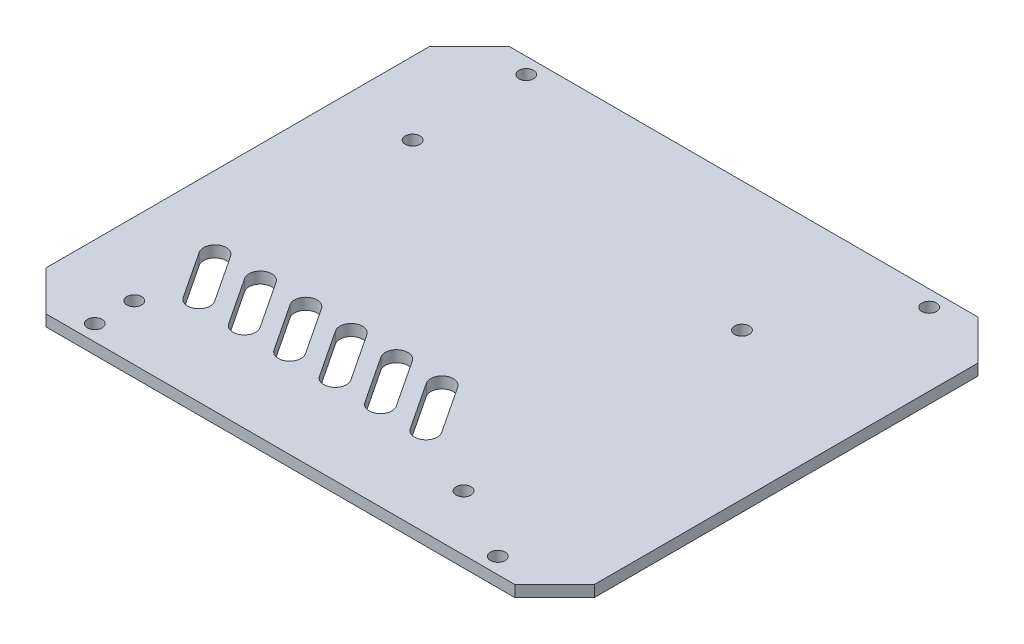
SolidWorks part; units mm, degrees
ref_plane "前视基准面" through (0, 0, 0) normal (0, 0, 1) x (1, 0, 0)
ref_plane "上视基准面" through (0, 0, 0) normal (0, 1, 0) x (1, 0, 0)
ref_plane "右视基准面" through (0, 0, 0) normal (1, 0, 0) x (0, 0, -1)
sketch "草图1" plane through (0, -19.39, 0) normal (0, -1, 0) x (1, 0, 0)
  line L16 (-51.8, -40.2958) -> (-44.7958, -47.3)
  line L17 (-44.7958, -47.3) -> (37.7958, -47.3)
  line L18 (37.7958, -47.3) -> (44.8, -40.2958)
  line L19 (44.8, -40.2958) -> (44.8, 27.2958)
  line L20 (44.8, 27.2958) -> (37.7958, 34.3)
  line L21 (-51.8, 27.2958) -> (-51.8, -40.2958)
  line L22 (37.7958, 34.3) -> (-44.7958, 34.3)
  line L23 (-44.7958, 34.3) -> (-51.8, 27.2958)
  line L24 (-51.8, -40.2958) -> (-44.7958, -47.3)
  line L25 (-44.7958, -47.3) -> (37.7958, -47.3)
  line L26 (37.7958, -47.3) -> (44.8, -40.2958)
  line L27 (44.8, -40.2958) -> (44.8, 27.2958)
  line L28 (44.8, 27.2958) -> (37.7958, 34.3)
  line L29 (-51.8, 27.2958) -> (-51.8, -40.2958)
  line L30 (37.7958, 34.3) -> (-44.7958, 34.3)
  line L31 (-44.7958, 34.3) -> (-51.8, 27.2958)
  dimension "D2" = 96.6
  dimension "D3" = 81.6
  dimension "D1" = 0.2
extrude "凸台-拉伸1" add sketch "草图1" along normal blind 2
sketch "草图2" plane through (0, -21.39, 0) normal (0, -1, 0) x (1, 0, 0)
  circle A0 centre (-39.0116, -24.5) radius 1.3
  circle A1 centre (19, -24.5) radius 1.3
  circle A2 centre (-39.0116, 24.5352) radius 1.3
  circle A3 centre (19, 24.5352) radius 1.3
  dimension "D1" = 2.6
extrude "切除-拉伸1" cut sketch "草图2" against normal up to next
sketch "草图3" plane through (0, -21.39, 0) normal (0, -1, 0) x (1, 0, 0)
  circle A0 centre (32, -44.5) radius 1.3 construction
  circle A1 centre (-39, -44.5) radius 1.3 construction
  circle A2 centre (32, 31.5) radius 1.3 construction
  circle A3 centre (-39, 31.5) radius 1.3 construction
  circle A4 centre (32, -44.5) radius 1.3
  circle A5 centre (-39, -44.5) radius 1.3
  circle A6 centre (32, 31.5) radius 1.3
  circle A7 centre (-39, 31.5) radius 1.3
extrude "切除-拉伸2" cut sketch "草图3" against normal up to next
sketch "草图4" plane through (0, -21.39, 0) normal (0, -1, 0) x (1, 0, 0)
  line L0 (-38.9928, 31.6194) -> (-39.0044, 24.6546) construction
  line L1 (-39.0282, 10.3) -> (-33.5143, 18.6425) construction
  line L2 (-40.6967, 11.4028) -> (-35.1828, 19.7453)
  line L3 (-37.3597, 9.1972) -> (-31.8458, 17.5397)
  line L5 (37.7958, 34.3) -> (-44.7958, 34.3) construction
  line L6 (-31.0282, 10.3) -> (-25.5143, 18.6425) construction
  line L9 (-32.6967, 11.4028) -> (-27.1828, 19.7453)
  line L12 (-29.3597, 9.1972) -> (-23.8458, 17.5397)
  line L15 (-23.0282, 10.3) -> (-17.5143, 18.6425) construction
  line L18 (-24.6967, 11.4028) -> (-19.1828, 19.7453)
  line L21 (-21.3597, 9.1972) -> (-15.8458, 17.5397)
  line L22 (-15.0282, 10.3) -> (-9.5143, 18.6425) construction
  line L23 (-16.6967, 11.4028) -> (-11.1828, 19.7453)
  line L24 (-13.3597, 9.1972) -> (-7.8458, 17.5397)
  line L25 (-7.0282, 10.3) -> (-1.5143, 18.6425) construction
  line L26 (-8.6967, 11.4028) -> (-3.1828, 19.7453)
  line L27 (-5.3597, 9.1972) -> (0.1542, 17.5397)
  line L28 (0.9718, 10.3) -> (6.4857, 18.6425) construction
  line L29 (-0.6967, 11.4028) -> (4.8172, 19.7453)
  line L30 (2.6403, 9.1972) -> (8.1542, 17.5397)
  arc A0 (-40.6967, 11.4028) -> (-37.3597, 9.1972) centre (-39.0282, 10.3) ccw
  arc A1 (-31.8458, 17.5397) -> (-35.1828, 19.7453) centre (-33.5143, 18.6425) ccw
  arc A12 (-32.6967, 11.4028) -> (-29.3597, 9.1972) centre (-31.0282, 10.3) ccw
  arc A13 (-23.8458, 17.5397) -> (-27.1828, 19.7453) centre (-25.5143, 18.6425) ccw
  arc A14 (-24.6967, 11.4028) -> (-21.3597, 9.1972) centre (-23.0282, 10.3) ccw
  arc A15 (-15.8458, 17.5397) -> (-19.1828, 19.7453) centre (-17.5143, 18.6425) ccw
  arc A16 (-16.6967, 11.4028) -> (-13.3597, 9.1972) centre (-15.0282, 10.3) ccw
  arc A17 (-7.8458, 17.5397) -> (-11.1828, 19.7453) centre (-9.5143, 18.6425) ccw
  arc A18 (-8.6967, 11.4028) -> (-5.3597, 9.1972) centre (-7.0282, 10.3) ccw
  arc A19 (0.1542, 17.5397) -> (-3.1828, 19.7453) centre (-1.5143, 18.6425) ccw
  arc A20 (-0.6967, 11.4028) -> (2.6403, 9.1972) centre (0.9718, 10.3) ccw
  arc A21 (8.1542, 17.5397) -> (4.8172, 19.7453) centre (6.4857, 18.6425) ccw
  point P6 (-36.2713, 14.4713)
  point P15 (-28.2713, 14.4713)
  point P22 (-20.2713, 14.4713)
  point P29 (-12.2713, 14.4713)
  point P36 (-4.2713, 14.4713)
  point P43 (3.7287, 14.4713)
  dimension "D1" = 2
  dimension "D2" = 10
  dimension "D3" = 5.5
  dimension "D4" = 12.8
  dimension "D5" = 24
  dimension "D6" = 6
extrude "切除-拉伸3" cut sketch "草图4" against normal up to next
sketch "草图5" plane through (0, -21.39, 0) normal (0, -1, 0) x (1, 0, 0)
sketch_block_instance "块1-1"
sketch_block "块1"
sketch "草图6" plane through (0, -19.39, 0) normal (0, 1, 0) x (1, 0, 0)
  line L0 (-39.0322, 2.6968) -> (-34.8198, 0.2624) construction
  line L1 (-34.177, 0.2624) -> (-29.9873, 2.7014) construction
  line L2 (-29.9828, 3.2622) -> (-34.0539, 5.6966) construction
  line L3 (-29.6682, 9.5398) -> (-30.5435, 10.0367) construction
  line L4 (-30.6757, 9.9592) -> (-30.6757, 7.9487) construction
  line L5 (-30.6301, 7.8712) -> (-29.7548, 7.3788) construction
  line L6 (-29.6226, 7.4564) -> (-29.6226, 9.4623) construction
  line L7 (-33.3108, 9.1249) -> (-33.3108, 8.049) construction
  line L8 (-33.2652, 7.9715) -> (-32.8731, 7.7527) construction
  line L9 (-32.8458, 9.0109) -> (-33.2652, 9.2207) construction
  line L10 (-33.2652, 9.2207) -> (-33.2652, 10.0868) construction
  line L11 (-32.791, 9.8224) -> (-33.2652, 10.0868) construction
  line L12 (-34.3274, 7.7345) -> (-32.823, 6.8819) construction
  line L13 (-34.373, 12.0335) -> (-34.373, 7.8119) construction
  line L14 (-33.3563, 11.6095) -> (-34.2408, 12.111) construction
  line L15 (-33.3108, 10.1644) -> (-33.3108, 11.532) construction
  line L16 (-33.3108, 9.1249) -> (-33.3108, 10.1644) construction
  line L17 (-17.9609, 5.9474) -> (-18.6265, 5.6829) construction
  line L18 (-17.7011, 5.0538) -> (-17.0627, 4.2514) construction
  line L19 (-19.6477, 6.6221) -> (-18.9684, 6.9093) construction
  line L20 (-20.2085, 7.429) -> (-20.9333, 8.3134) construction
  line L21 (-10.1469, 9.1523) -> (-9.7593, 9.1523) construction
  line L22 (-5.5196, 7.1144) -> (-5.5196, 7.7664) construction
  line L23 (-26.0439, 6.3576) -> (-26.0439, 4.2651) construction
  line L24 (-26.0439, 4.2651) -> (-25.2871, 4.2651) construction
  line L25 (-25.2597, 6.3576) -> (-26.0439, 6.3576) construction
  line L26 (-26.7095, 3.7272) -> (-26.7095, 8.979) construction
  line L27 (-26.7095, 8.979) -> (-26.0439, 8.979) construction
  line L28 (-26.0439, 8.979) -> (-26.0439, 6.8956) construction
  line L29 (-26.0439, 6.8956) -> (-25.1731, 6.8956) construction
  line L30 (-25.2096, 3.7272) -> (-26.7095, 3.7272) construction
  line L31 (-33.1558, -0.189) -> (-33.8122, -0.5719) construction
  line L32 (-35.189, -0.5719) -> (-35.8455, -0.189) construction
  line L33 (-35.8455, -0.189) -> (-39.2511, 1.7759) construction
  line L34 (-39.2511, 1.7759) -> (-39.9076, 2.1543) construction
  line L35 (-40.596, 3.3442) -> (-40.596, 8.7967) construction
  line L36 (-39.9076, 9.9866) -> (-39.2511, 10.365) construction
  line L37 (-39.2511, 10.365) -> (-35.8455, 12.3299) construction
  line L38 (-35.8455, 12.3299) -> (-35.189, 12.7128) construction
  line L39 (-33.8122, 12.7128) -> (-33.1558, 12.3299) construction
  line L40 (-33.1558, 12.3299) -> (-29.7503, 10.365) construction
  line L41 (-29.7503, 10.365) -> (-29.0938, 9.9866) construction
  line L42 (-28.4054, 8.7967) -> (-28.4054, 3.3442) construction
  line L43 (-29.0938, 2.1543) -> (-29.7503, 1.7759) construction
  line L44 (-29.7503, 1.7759) -> (-33.1558, -0.189) construction
  line L45 (-5.3737, 8.5687) -> (-5.2826, 8.979) construction
  line L46 (-5.2826, 8.979) -> (-4.2431, 8.979) construction
  line L47 (-4.2431, 8.979) -> (-4.2431, 6.6631) construction
  line L48 (-7.6486, 5.3365) -> (-7.2018, 6.1753) construction
  line L49 (-5.4056, 8.5687) -> (-5.3737, 8.5687) construction
  line L50 (-8.0133, 5.8243) -> (-8.0133, 4.9034) construction
  line L51 (-8.0133, 4.9034) -> (-9.5086, 4.9034) construction
  line L52 (-11.3094, 7.3378) -> (-11.3094, 7.3652) construction
  line L53 (-11.3869, 8.8286) -> (-11.3869, 8.8651) construction
  line L54 (-9.5178, 8.1767) -> (-10.1606, 8.1767) construction
  line L55 (-8.6424, 5.8243) -> (-8.0133, 5.8243) construction
  line L56 (-13.8761, 4.9034) -> (-13.8761, 7.5749) construction
  line L57 (-15.0295, 7.2649) -> (-15.0295, 4.9034) construction
  line L58 (-15.0295, 4.9034) -> (-16.3014, 4.9034) construction
  line L59 (-16.3014, 4.9034) -> (-16.3014, 7.4245) construction
  line L60 (-13.7575, 8.4183) -> (-13.7302, 8.4183) construction
  line L61 (-13.7302, 8.4183) -> (-13.639, 8.979) construction
  line L62 (-13.639, 8.979) -> (-12.5996, 8.979) construction
  line L63 (-12.5996, 8.979) -> (-12.5996, 4.9034) construction
  line L64 (-12.5996, 4.9034) -> (-13.8761, 4.9034) construction
  line L65 (-21.7265, 8.979) -> (-21.7265, 5.0857) construction
  line L66 (-22.3785, 8.979) -> (-21.7265, 8.979) construction
  line L67 (-22.3785, 5.0857) -> (-22.3785, 8.979) construction
  line L68 (-21.7265, 5.0857) -> (-22.3785, 5.0857) construction
  line L69 (-3.4042, 8.979) -> (-2.1368, 8.979) construction
  line L70 (-2.1368, 8.979) -> (-2.1368, 6.6494) construction
  line L71 (-0.8102, 5.9838) -> (-0.596, 4.8851) construction
  line L72 (-2.2508, 5.61) -> (-2.2782, 5.61) construction
  line L73 (-2.2782, 5.61) -> (-2.3648, 4.9034) construction
  line L74 (-2.3648, 4.9034) -> (-3.4042, 4.9034) construction
  line L75 (-3.4042, 4.9034) -> (-3.4042, 8.979) construction
  line L76 (-39.0322, 2.6968) -> (-34.8198, 0.2624)
  line L77 (-34.177, 0.2624) -> (-29.9873, 2.7014)
  line L78 (-29.9828, 3.2622) -> (-34.0539, 5.6966)
  line L79 (-29.6682, 9.5398) -> (-30.5435, 10.0367)
  line L80 (-30.6757, 9.9592) -> (-30.6757, 7.9487)
  line L81 (-30.6301, 7.8712) -> (-29.7548, 7.3788)
  line L82 (-29.6226, 7.4564) -> (-29.6226, 9.4623)
  line L83 (-33.3108, 9.1249) -> (-33.3108, 8.049)
  line L84 (-33.2652, 7.9715) -> (-32.8731, 7.7527)
  line L85 (-32.8458, 9.0109) -> (-33.2652, 9.2207)
  line L86 (-33.2652, 9.2207) -> (-33.2652, 10.0868)
  line L87 (-32.791, 9.8224) -> (-33.2652, 10.0868)
  line L88 (-34.3274, 7.7345) -> (-32.823, 6.8819)
  line L89 (-34.373, 12.0335) -> (-34.373, 7.8119)
  line L90 (-33.3563, 11.6095) -> (-34.2408, 12.111)
  line L91 (-33.3108, 10.1644) -> (-33.3108, 11.532)
  line L92 (-33.3108, 9.1249) -> (-33.3108, 10.1644)
  line L93 (-17.9609, 5.9474) -> (-18.6265, 5.6829)
  line L94 (-17.7011, 5.0538) -> (-17.0627, 4.2514)
  line L95 (-19.6477, 6.6221) -> (-18.9684, 6.9093)
  line L96 (-20.2085, 7.429) -> (-20.9333, 8.3134)
  line L97 (-10.1469, 9.1523) -> (-9.7593, 9.1523)
  line L98 (-5.5196, 7.1144) -> (-5.5196, 7.7664)
  line L99 (-26.0439, 6.3576) -> (-26.0439, 4.2651)
  line L100 (-26.0439, 4.2651) -> (-25.2871, 4.2651)
  line L101 (-25.2597, 6.3576) -> (-26.0439, 6.3576)
  line L102 (-26.7095, 3.7272) -> (-26.7095, 8.979)
  line L103 (-26.7095, 8.979) -> (-26.0439, 8.979)
  line L104 (-26.0439, 8.979) -> (-26.0439, 6.8956)
  line L105 (-26.0439, 6.8956) -> (-25.1731, 6.8956)
  line L106 (-25.2096, 3.7272) -> (-26.7095, 3.7272)
  line L107 (-33.1558, -0.189) -> (-33.8122, -0.5719)
  line L108 (-35.189, -0.5719) -> (-35.8455, -0.189)
  line L109 (-35.8455, -0.189) -> (-39.2511, 1.7759)
  line L110 (-39.2511, 1.7759) -> (-39.9076, 2.1543)
  line L111 (-40.596, 3.3442) -> (-40.596, 8.7967)
  line L112 (-39.9076, 9.9866) -> (-39.2511, 10.365)
  line L113 (-39.2511, 10.365) -> (-35.8455, 12.3299)
  line L114 (-35.8455, 12.3299) -> (-35.189, 12.7128)
  line L115 (-33.8122, 12.7128) -> (-33.1558, 12.3299)
  line L116 (-33.1558, 12.3299) -> (-29.7503, 10.365)
  line L117 (-29.7503, 10.365) -> (-29.0938, 9.9866)
  line L118 (-28.4054, 8.7967) -> (-28.4054, 3.3442)
  line L119 (-29.0938, 2.1543) -> (-29.7503, 1.7759)
  line L120 (-29.7503, 1.7759) -> (-33.1558, -0.189)
  line L121 (-5.3737, 8.5687) -> (-5.2826, 8.979)
  line L122 (-5.2826, 8.979) -> (-4.2431, 8.979)
  line L123 (-4.2431, 8.979) -> (-4.2431, 6.6631)
  line L124 (-7.6486, 5.3365) -> (-7.2018, 6.1753)
  line L125 (-5.4056, 8.5687) -> (-5.3737, 8.5687)
  line L126 (-8.0133, 5.8243) -> (-8.0133, 4.9034)
  line L127 (-8.0133, 4.9034) -> (-9.5086, 4.9034)
  line L128 (-11.3094, 7.3378) -> (-11.3094, 7.3652)
  line L129 (-11.3869, 8.8286) -> (-11.3869, 8.8651)
  line L130 (-9.5178, 8.1767) -> (-10.1606, 8.1767)
  line L131 (-8.6424, 5.8243) -> (-8.0133, 5.8243)
  line L132 (-13.8761, 4.9034) -> (-13.8761, 7.5749)
  line L133 (-15.0295, 7.2649) -> (-15.0295, 4.9034)
  line L134 (-15.0295, 4.9034) -> (-16.3014, 4.9034)
  line L135 (-16.3014, 4.9034) -> (-16.3014, 7.4245)
  line L136 (-13.7575, 8.4183) -> (-13.7302, 8.4183)
  line L137 (-13.7302, 8.4183) -> (-13.639, 8.979)
  line L138 (-13.639, 8.979) -> (-12.5996, 8.979)
  line L139 (-12.5996, 8.979) -> (-12.5996, 4.9034)
  line L140 (-12.5996, 4.9034) -> (-13.8761, 4.9034)
  line L141 (-21.7265, 8.979) -> (-21.7265, 5.0857)
  line L142 (-22.3785, 8.979) -> (-21.7265, 8.979)
  line L143 (-22.3785, 5.0857) -> (-22.3785, 8.979)
  line L144 (-21.7265, 5.0857) -> (-22.3785, 5.0857)
  line L145 (-3.4042, 8.979) -> (-2.1368, 8.979)
  line L146 (-2.1368, 8.979) -> (-2.1368, 6.6494)
  line L147 (-0.8102, 5.9838) -> (-0.596, 4.8851)
  line L148 (-2.2508, 5.61) -> (-2.2782, 5.61)
  line L149 (-2.2782, 5.61) -> (-2.3648, 4.9034)
  line L150 (-2.3648, 4.9034) -> (-3.4042, 4.9034)
  line L151 (-3.4042, 4.9034) -> (-3.4042, 8.979)
  spline S0 degree 3 poles (1947.2043, 259.0221) (-2040.5975, -86.3945) (1971.5647, -86.1046) (-2015.9835, 259.8919) knots -24.014283 -24.014283 -24.014283 -24.014283 31.060476 31.060476 31.060476 31.060476 only from (-34.8198, 0.2624) to (-34.177, 0.2624) construction
  spline S1 degree 3 poles (-178.8618, 1996.4067) (-13.3017, -2002.4803) (85.7628, 2005.1657) (-277.1173, -1980.6649) knots -12.069605 -12.069605 -12.069605 -12.069605 23.053377 23.053377 23.053377 23.053377 only from (-29.9873, 2.7014) to (-29.9828, 3.2622) construction
  spline S2 degree 3 poles (-2011.9647, -280.5218) (1973.0796, 101.2598) (-2042.0834, 101.2623) (1942.99, -280.5143) knots -16.956312 -16.956312 -16.956312 -16.956312 31.955994 31.955994 31.955994 31.955994 only from (-34.0539, 5.6966) to (-34.9429, 5.6966) construction
  spline S3 degree 2 poles (1696.8938, 1005.9909) (-1772.9636, -998.1959) (1692.7429, 1003.6514) knots -19.544322 -19.544322 -19.544322 21.524182 21.524182 21.524182 only from (-34.9429, 5.6966) to (-39.0732, 3.3123) construction
  spline S4 degree 3 poles (312.9236, -1964.6822) (-255.5836, 1997.2947) (39.8207, -2001.4292) (20.6091, 2000.9771) knots -16.033039 -16.033039 -16.033039 -16.033039 19.060221 19.060221 19.060221 19.060221 only from (-39.0732, 3.3123) to (-39.0322, 2.6968) construction
  spline S5 degree 3 poles (1612.1466, 1139.1382) (-173.749, 124.6775) (-29.5451, -1.4055) (-29.5451, 6.2482) (-29.5451, 12.5795) (-131.1047, 41.0713) (891.7703, -1766.7786) knots -20.983072 -20.983072 -20.983072 -20.983072 3 3 3 23.1269 23.1269 23.1269 23.1269 only from (-30.1469, 6.0431) to (-30.1469, 7.1281) construction
  spline S6 degree 3 poles (-1593.6748, -1232.4433) (112.4759, -108.2288) (-30.7532, 14.45) (-30.7532, 6.9321) (-30.7532, 0.2328) (76.6581, -24.0346) (-1002.5668, 1752.6044) knots -22.899222 -22.899222 -22.899222 -22.899222 1 1 1 21.696321 21.696321 21.696321 21.696321 only from (-30.1469, 7.1281) to (-30.1469, 6.0431) construction
  spline S7 degree 3 poles (-1735.267, -1035.1971) (1720.3132, 981.2712) (-1822.079, -884.2768) (1795.5461, 824.5182) knots -24.864003 -24.864003 -24.864003 -24.864003 29.805716 29.805716 29.805716 29.805716 only from (-30.5435, 10.0367) to (-30.6757, 9.9592) construction
  spline S8 degree 3 poles (1803.8452, -787.8206) (-1835.1338, 879.7734) (1736.3613, -937.8925) (-1752.2845, 1025.0132) knots -52.644856 -52.644856 -52.644856 -52.644856 63.422153 63.422153 63.422153 63.422153 only from (-30.6757, 7.9487) to (-30.6301, 7.8712) construction
  spline S9 degree 3 poles (1675.9971, 1050.9308) (-1781.5786, -962.103) (1762.6814, 899.8753) (-1856.6746, -805.2277) knots -20.869425 -20.869425 -20.869425 -20.869425 33.809897 33.809897 33.809897 33.809897 only from (-29.7548, 7.3788) to (-29.6226, 7.4564) construction
  spline S10 degree 3 poles (-1017.153, 1748.416) (898.1967, -1765.8691) (-895.3334, 1815.971) (771.5167, -1822.726) knots -45.73326 -45.73326 -45.73326 -45.73326 46.535072 46.535072 46.535072 46.535072 only from (-29.6226, 9.4623) to (-29.6682, 9.5398) construction
  spline S11 degree 3 poles (1241.4728, -1544.2848) (-126.4363, -19.7603) (-21.5989, 9.5171) (-21.5989, 3.8639) (-21.5989, -3.1211) (-150.7291, 66.7677) (1747.5616, 931.244) knots -20.398043 -20.398043 -20.398043 -20.398043 3 3 3 28.967808 28.967808 28.967808 28.967808 only from (-22.0502, 4.2833) to (-22.0502, 3.44) construction
  spline S12 degree 3 poles (-1791.638, 931.233) (106.6275, 66.7672) (-22.5016, -3.1211) (-22.5016, 3.8639) (-22.5016, 9.5171) (82.3355, -19.7602) (-1285.567, -1544.2778) knots -24.967698 -24.967698 -24.967698 -24.967698 1 1 1 24.398007 24.398007 24.398007 24.398007 only from (-22.0502, 3.44) to (-22.0502, 4.2833) construction
  spline S13 degree 3 poles (953.112, -1731.5311) (-960.0271, 1783.9495) (831.3079, -1798.9714) (-833.3757, 1840.6921) knots -41.715469 -41.715469 -41.715469 -41.715469 50.515238 50.515238 50.515238 50.515238 only from (-33.3108, 8.049) to (-33.2652, 7.9715) construction
  spline S14 degree 3 poles (345.3515, -1953.7628) (-656.074, 2008.4671) (704.4049, -1945.0024) (-795.7723, 1856.1671) knots -18.836401 -18.836401 -18.836401 -18.836401 26.867419 26.867419 26.867419 26.867419 only from (-32.8731, 7.7527) to (-32.0799, 7.9031) construction
  spline S15 degree 3 poles (393.8329, 1947.428) (-1017.3565, -1766.8215) (1294.138, 1559.3727) (-1541.9229, -1298.5467) knots -37.738435 -37.738435 -37.738435 -37.738435 30.849118 30.849118 30.849118 30.849118 only from (-32.0799, 7.9031) to (-32.8458, 9.0109) construction
  spline S16 degree 3 poles (-1970.6267, 490.4514) (1900.3877, -652.3893) (-1909.3139, 822.203) (1735.9268, -921.8099) knots -2.984455 -2.984455 -2.984455 -2.984455 24.908291 24.908291 24.908291 24.908291 only from (-31.0405, 7.315) to (-32.791, 9.8224) construction
  spline S17 degree 3 poles (1301.0551, -1483.1694) (-1380.7778, 1570.3517) (1272.9624, -1585.6466) (-1251.2088, 1591.7607) knots -4.177868 -4.177868 -4.177868 -4.177868 21.267464 21.267464 21.267464 21.267464 only from (-32.823, 6.8819) to (-31.0405, 7.315) construction
  spline S18 degree 3 poles (-426.7908, -1953.0944) (416.9018, 1960.3516) (-543.6183, -1930.3492) (531.9657, 1925.7159) knots -40.574336 -40.574336 -40.574336 -40.574336 54.224541 54.224541 54.224541 54.224541 only from (-34.373, 7.8119) to (-34.3274, 7.7345) construction
  spline S19 degree 3 poles (-1739.7201, -1031.8845) (1717.3311, 982.0362) (-1826.4475, -880.8273) (1792.473, 825.1567) knots -21.867988 -21.867988 -21.867988 -21.867988 32.80886 32.80886 32.80886 32.80886 only from (-34.2408, 12.111) to (-34.373, 12.0335) construction
  spline S20 degree 3 poles (1326.5597, 1477.8337) (-1443.7748, -1422.5109) (1417.5131, 1403.8248) (-1515.2659, -1331.1895) knots -66.611259 -66.611259 -66.611259 -66.611259 68.63044 68.63044 68.63044 68.63044 only from (-33.3108, 11.532) to (-33.3563, 11.6095) construction
  spline S21 degree 3 poles (-1127.9465, 1668.9065) (1205.0665, -1581.8003) (-1320.6139, 1532.1331) (1326.4072, -1474.1074) knots -17.356672 -17.356672 -17.356672 -17.356672 19.212167 19.212167 19.212167 19.212167 only from (-18.6265, 5.6829) to (-19.4334, 5.0857) construction
  spline S22 degree 3 poles (1945.6237, -352.8331) (-1917.2958, 619.5498) (1753.4488, -897.6325) (-1594.6226, 1226.9154) knots -23.773694 -23.773694 -23.773694 -23.773694 31.399142 31.399142 31.399142 31.399142 only from (-19.4334, 5.0857) to (-18.7952, 4.6435) construction
  spline S23 degree 3 poles (-1957.8604, 491.3787) (1905.2875, -332.0334) (-1960.1859, 166.6666) (1980.2936, 44.6676) knots -22.175827 -22.175827 -22.175827 -22.175827 30.019969 30.019969 30.019969 30.019969 only from (-18.7952, 4.6435) to (-17.7011, 5.0538) construction
  spline S24 degree 3 poles (-1996.9289, 274.3391) (2008.3741, -55.5657) (-2041.9478, -141.8187) (1949.9756, 346.3582) knots -14.985955 -14.985955 -14.985955 -14.985955 26.624596 26.624596 26.624596 26.624596 only from (-17.0627, 4.2514) to (-18.7952, 3.5448) construction
  spline S25 degree 3 poles (-959.5674, 1764.5293) (1176.2874, -1603.5878) (-1432.6495, 1427.6748) (1567.7803, -1205.173) knots -7.558703 -7.558703 -7.558703 -7.558703 20.482777 20.482777 20.482777 20.482777 only from (-18.7952, 3.5448) to (-20.7327, 5.1587) construction
  spline S26 degree 3 poles (1924.0493, -458.54) (-2016.5165, 343.495) (1995.4741, -211.501) (-2016.1303, 116.1959) knots -7.852621 -7.852621 -7.852621 -7.852621 24.144848 24.144848 24.144848 24.144848 only from (-20.7327, 5.1587) to (-19.6477, 6.6221) construction
  spline S27 degree 3 poles (615.0637, -1888.8545) (-795.6899, 1841.0297) (868.9978, -1778.6578) (-986.0957, 1757.28) knots -9.138526 -9.138526 -9.138526 -9.138526 27.25787 27.25787 27.25787 27.25787 only from (-18.9684, 6.9093) to (-18.2162, 7.5111) construction
  spline S28 degree 3 poles (215.7009, 1986.9997) (-654.6592, -1923.8751) (894.6606, 1828.6602) (-1110.216, -1665.8008) knots -22.542702 -22.542702 -22.542702 -22.542702 37.658646 37.658646 37.658646 37.658646 only from (-18.2162, 7.5111) to (-18.9137, 7.9761) construction
  spline S29 degree 3 poles (-1605.429, -1208.7716) (1666.7814, 1140.7416) (-1773.5402, -1019.3674) (1765.9801, 905.5471) knots -8.791084 -8.791084 -8.791084 -8.791084 32.386114 32.386114 32.386114 32.386114 only from (-18.9137, 7.9761) to (-20.2085, 7.429) construction
  spline S30 degree 3 poles (1966.5787, -197.5818) (-2051.7497, -0.967) (2002.48, 224.4874) (-1974.8286, -400.794) knots -6.294928 -6.294928 -6.294928 -6.294928 33.756853 33.756853 33.756853 33.756853 only from (-20.9333, 8.3134) to (-18.9411, 9.0793) construction
  spline S31 degree 3 poles (124.1341, -1982.3989) (-457.1442, 1958.1164) (708.8959, -1855.2284) (-1015.0804, 1736.3895) knots 0.697384 0.697384 0.697384 0.697384 28.978211 28.978211 28.978211 28.978211 only from (-18.9411, 9.0793) to (-16.9033, 7.4108) construction
  spline S32 degree 3 poles (-1495.2544, 1354.2838) (1523.5493, -1377.9736) (-1538.1686, 1424.3054) (1353.4505, -1448.6746) knots -4.734801 -4.734801 -4.734801 -4.734801 40.265101 40.265101 40.265101 40.265101 only from (-16.9033, 7.4108) to (-17.9609, 5.9474) construction
  spline S33 degree 3 poles (-1961.8056, -418.0731) (126.6492, -101.6131) (-10.6711, 16.7967) (-10.6711, 6.2847) (-10.6711, -3.9538) (125.3735, 107.9903) (-1932.7785, 547.0377) knots -21.79377 -21.79377 -21.79377 -21.79377 3 3 3 27.67833 27.67833 27.67833 27.67833 only from (-10.156, 6.923) to (-10.156, 5.6556) construction
  spline S34 degree 3 poles (1882.1607, 641.7029) (-158.572, 123.862) (-9.6409, -4.6535) (-9.6409, 6.2847) (-9.6409, 17.5385) (-160.5965, -118.9677) (1923.9331, -488.0552) knots -25.364902 -25.364902 -25.364902 -25.364902 1 1 1 27.543492 27.543492 27.543492 27.543492 only from (-10.156, 5.6556) to (-10.156, 6.923) construction
  spline S35 degree 3 poles (398.3769, -1946.8651) (-621.0655, 1916.7975) (746.5301, -1849.6014) (-860.4662, 1818.6943) knots -20.367991 -20.367991 -20.367991 -20.367991 27.043685 27.043685 27.043685 27.043685 only from (-9.7593, 9.1523) to (-9.1667, 9.4441) construction
  spline S36 degree 3 poles (-1851.6901, 784.2948) (1770.8918, -932.7585) (-1685.1957, 1125.6418) (1512.1872, -1283.8884) knots -14.155704 -14.155704 -14.155704 -14.155704 26.455766 26.455766 26.455766 26.455766 only from (-9.1667, 9.4441) to (-10.0557, 9.8954) construction
  spline S37 degree 3 poles (-1999.7746, -177.9397) (2048.5506, 17.7992) (-2059.7856, 149.4036) (1971.6374, -249.0633) knots -24.53604 -24.53604 -24.53604 -24.53604 22.203045 22.203045 22.203045 22.203045 only from (-10.0557, 9.8954) to (-10.9219, 9.4668) construction
  spline S38 degree 3 poles (335.4233, 1977.3974) (-130.5762, -1935.4278) (-138.8194, 1950.0115) (386.7962, -1948.2187) knots -42.090152 -42.090152 -42.090152 -42.090152 46.007634 46.007634 46.007634 46.007634 only from (-10.9219, 9.4668) to (-10.7304, 9.1021) construction
  spline S39 degree 3 poles (-2000.164, -195.6542) (1968.231, 177.2652) (-1992.5781, -127.132) (1986.8184, 117.9013) knots -23.761314 -23.761314 -23.761314 -23.761314 27.411452 27.411452 27.411452 27.411452 only from (-10.7304, 9.1021) to (-10.1469, 9.1523) construction
  spline S40 degree 3 poles (1900.4815, 611.268) (-1853.5024, -713.4995) (1804.2956, 824.4669) (-1796.5625, -882.5407) knots -25.691977 -25.691977 -25.691977 -25.691977 25.491412 25.491412 25.491412 25.491412 only from (-5.5196, 7.7664) to (-6.135, 8.09) construction
  spline S41 degree 3 poles (-2003.4629, -52.8338) (2017.9029, -136.2777) (-2009.5197, 324.3726) (1939.2706, -450.8338) knots -29.27083 -29.27083 -29.27083 -29.27083 28.779665 28.779665 28.779665 28.779665 only from (-6.135, 8.09) to (-6.5727, 7.739) construction
  spline S42 degree 3 poles (-1965.4656, -395.4958) (1971.7383, 441.6954) (-1983.3474, -426.4496) (1951.4791, 419.1184) knots -18.272249 -18.272249 -18.272249 -18.272249 20.366917 20.366917 20.366917 20.366917 only from (-6.5727, 7.739) to (-5.5196, 7.1144) construction
  spline S43 degree 3 poles (-552.3477, -1916.0072) (39.6444, 1949.1893) (231.1798, -1947.9287) (-488.2476, 1949.0672) knots -16.951569 -16.951569 -16.951569 -16.951569 21.292276 21.292276 21.292276 21.292276 only from (-25.2871, 4.2651) to (-23.9011, 5.2681) construction
  spline S44 degree 3 poles (74.9674, -1978.7796) (-669.1868, 1491.4113) (1220.9961, -1007.5518) (-1925.4997, 576.7533) knots -20.703775 -20.703775 -20.703775 -20.703775 29.911591 29.911591 29.911591 29.911591 only from (-23.9011, 5.2681) to (-25.2597, 6.3576) construction
  spline S45 degree 3 poles (1967.7044, -102.3152) (-2083.6001, -202.2982) (1987.7708, 465.393) (-1913.3422, -643.1952) knots -12.662635 -12.662635 -12.662635 -12.662635 20.708978 20.708978 20.708978 20.708978 only from (-25.1731, 6.8956) to (-23.2401, 5.2681) construction
  spline S46 degree 3 poles (-1462.7137, 1393.5071) (1511.2501, -1404.3078) (-1580.4996, 1407.0991) (1432.7296, -1365.1759) knots -7.615095 -7.615095 -7.615095 -7.615095 23.693651 23.693651 23.693651 23.693651 only from (-23.2401, 5.2681) to (-25.2096, 3.7272) construction
  spline S47 degree 3 poles (-1986.2159, -424.6605) (1872.5149, 650.7296) (-1856.7008, -859.0204) (1668.1443, 1044.8861) knots -40.403395 -40.403395 -40.403395 -40.403395 46.454358 46.454358 46.454358 46.454358 only from (-33.8122, -0.5719) to (-34.5006, -0.7543) construction
  spline S48 degree 3 poles (-1740.3489, 1039.5921) (1790.0962, -854.0172) (-1943.0897, 646.2372) (1918.0006, -420.927) knots -38.373718 -38.373718 -38.373718 -38.373718 48.302597 48.302597 48.302597 48.302597 only from (-34.5006, -0.7543) to (-35.189, -0.5719) construction
  spline S49 degree 3 poles (-754.8971, 1867.8409) (885.9932, -1784.6) (-1157.7277, 1677.1962) (1246.9181, -1524.5355) knots -12.834285 -12.834285 -12.834285 -12.834285 29.798641 29.798641 29.798641 29.798641 only from (-39.9076, 2.1543) to (-40.596, 3.3442) construction
  spline S50 degree 3 poles (1310.7611, 1480.2732) (-1219.4015, -1620.1293) (943.9093, 1763.7167) (-807.2491, -1834.6442) knots -11.169927 -11.169927 -11.169927 -11.169927 32.277267 32.277267 32.277267 32.277267 only from (-40.596, 8.7967) to (-39.9076, 9.9866) construction
  spline S51 degree 3 poles (1829.5545, -704.5958) (-1983.3127, 518.655) (1959.6502, -271.0062) (-2031.7382, 64.4568) knots -28.630568 -28.630568 -28.630568 -28.630568 59.634843 59.634843 59.634843 59.634843 only from (-35.189, 12.7128) to (-34.5006, 12.8952) construction
  spline S52 degree 3 poles (1962.7022, 65.7414) (-2028.2181, -273.3756) (1913.3784, 521.8911) (-1897.0742, -708.4939) knots -29.74703 -29.74703 -29.74703 -29.74703 58.724161 58.724161 58.724161 58.724161 only from (-34.5006, 12.8952) to (-33.8122, 12.7128) construction
  spline S53 degree 3 poles (611.3262, -1882.3455) (-897.4898, 1821.8566) (1049.2417, -1687.0258) (-1295.1838, 1553.5314) knots -2.467628 -2.467628 -2.467628 -2.467628 41.506639 41.506639 41.506639 41.506639 only from (-29.0938, 9.9866) to (-28.4054, 8.7967) construction
  spline S54 degree 3 poles (-1230.5684, -1592.4268) (988.9215, 1738.3623) (-842.904, -1836.9675) (564.0724, 1910.0048) knots -0.095652 -0.095652 -0.095652 -0.095652 42.997123 42.997123 42.997123 42.997123 only from (-28.4054, 3.3442) to (-29.0938, 2.1543) construction
  spline S55 degree 3 poles (-1430.5573, 1407.5659) (1723.1127, -1481.9909) (-1919.6145, 1389.7982) (1763.4855, -917.7581) knots -7.107453 -7.107453 -7.107453 -7.107453 39.300169 39.300169 39.300169 39.300169 only from (-4.2431, 6.6631) to (-5.8934, 4.8031) construction
  spline S56 degree 3 poles (200.3126, 1993.6618) (-113.4143, -2029.6162) (37.9701, 2047.0917) (-46.8978, -1994.2146) knots -24.475698 -24.475698 -24.475698 -24.475698 28.452112 28.452112 28.452112 28.452112 only from (-5.8934, 4.8031) to (-7.6486, 5.3365) construction
  spline S57 degree 3 poles (-1933.6669, -520.0604) (1769.2026, 770.3694) (-1678.914, -975.8177) (1607.9896, 1184.3814) knots -29.345565 -29.345565 -29.345565 -29.345565 33.949512 33.949512 33.949512 33.949512 only from (-7.2018, 6.1753) to (-6.135, 5.8197) construction
  spline S58 degree 3 poles (-1709.7987, 1053.3931) (1749.403, -1046.8479) (-1793.7464, 1008.7473) (1793.1121, -866.6254) knots -20.675466 -20.675466 -20.675466 -20.675466 32.208493 32.208493 32.208493 32.208493 only from (-6.135, 5.8197) to (-5.5196, 6.3394) construction
  spline S59 degree 3 poles (1975.7527, -248.8039) (-1868.9813, 512.6632) (1631.6647, -894.331) (-1295.7423, 1512.4535) knots -12.733532 -12.733532 -12.733532 -12.733532 25.757539 25.757539 25.757539 25.757539 only from (-5.5196, 6.3394) to (-7.7854, 7.8393) construction
  spline S60 degree 3 poles (1042.4421, 1706.8309) (-834.6219, -1820.7719) (589.0356, 1925.2458) (-367.8223, -1955.7065) knots -11.03402 -11.03402 -11.03402 -11.03402 21.264003 21.264003 21.264003 21.264003 only from (-7.7854, 7.8393) to (-6.5727, 9.0793) construction
  spline S61 degree 3 poles (-582.1125, -1906.1013) (523.4678, 1965.3983) (-513.1262, -1956.0805) (513.8823, 1939.9285) knots -17.627726 -17.627726 -17.627726 -17.627726 33.245267 33.245267 33.245267 33.245267 only from (-6.5727, 9.0793) to (-5.4056, 8.5687) construction
  spline S62 degree 3 poles (-1930.5691, 559.3395) (1974.8488, -448.3348) (-2018.9786, 347.7304) (1976.7281, -218.5664) knots -33.500705 -33.500705 -33.500705 -33.500705 55.20773 55.20773 55.20773 55.20773 only from (-9.5086, 4.9034) to (-10.156, 4.8031) construction
  spline S63 degree 3 poles (-1999.2913, 198.6019) (2020.2524, -1.5641) (-2032.1384, -171.0059) (1955.7763, 357.6437) knots -3.872904 -3.872904 -3.872904 -3.872904 23.676976 23.676976 23.676976 23.676976 only from (-10.156, 4.8031) to (-11.8611, 6.2847) construction
  spline S64 degree 3 poles (1939.5115, 440.407) (-1940.4923, -577.4399) (1873.7743, 723.7895) (-1830.7521, -821.4821) knots -8.023341 -8.023341 -8.023341 -8.023341 31.752387 31.752387 31.752387 31.752387 only from (-11.8611, 6.2847) to (-11.3094, 7.3378) construction
  spline S65 degree 3 poles (-1329.9726, 1509.8665) (1428.2205, -1408.3534) (-1547.8279, 1317.3332) (1597.8765, -1177.5524) knots -10.762319 -10.762319 -10.762319 -10.762319 36.904963 36.904963 36.904963 36.904963 only from (-11.3094, 7.3652) to (-11.7608, 8.1265) construction
  spline S66 degree 3 poles (1690.5146, -1041.4074) (-1758.3489, 1014.3497) (1757.9984, -959.3158) (-1776.7351, 948.7003) knots -9.879735 -9.879735 -9.879735 -9.879735 41.23424 41.23424 41.23424 41.23424 only from (-11.7608, 8.1265) to (-11.3869, 8.8286) construction
  spline S67 degree 3 poles (-752.9374, 1842.3255) (1308.8718, -1353.5914) (-1702.759, 958.5145) (1892.0914, -582.47) knots -26.637538 -26.637538 -26.637538 -26.637538 53.487657 53.487657 53.487657 53.487657 only from (-11.3869, 8.8651) to (-11.9659, 9.6674) construction
  spline S68 degree 3 poles (1894.089, -594.3405) (-1996.6922, 519.1508) (2004.2706, -389.5025) (-1990.0486, 289.9866) knots 3.488718 3.488718 3.488718 3.488718 33.266204 33.266204 33.266204 33.266204 only from (-11.9659, 9.6674) to (-10.2563, 10.6932) construction
  spline S69 degree 3 poles (883.5316, -1769.7092) (-1265.933, 1528.3806) (1531.048, -1233.7757) (-1756.2499, 971.1381) knots 2.502912 2.502912 2.502912 2.502912 33.788332 33.788332 33.788332 33.788332 only from (-10.2563, 10.6932) to (-7.9495, 9.2207) construction
  spline S70 degree 3 poles (-1471.0119, 1372.7307) (1578.4938, -1482.6464) (-1566.0618, 1580.68) (1222.054, -1564.0225) knots 0.121158 0.121158 0.121158 0.121158 45.755216 45.755216 45.755216 45.755216 only from (-7.9495, 9.2207) to (-9.5178, 8.1767) construction
  spline S71 degree 3 poles (1988.9699, 46.517) (-2010.5704, -146.5098) (1966.0388, 323.2501) (-1936.5111, -524.1006) knots -22.92357 -22.92357 -22.92357 -22.92357 29.602258 29.602258 29.602258 29.602258 only from (-10.1606, 8.1767) to (-10.7623, 7.9031) construction
  spline S72 degree 3 poles (-533.5031, 1938.1422) (580.6394, -1888.8677) (-675.8787, 1879.566) (733.4353, -1848.486) knots -24.426858 -24.426858 -24.426858 -24.426858 29.596464 29.596464 29.596464 29.596464 only from (-10.7623, 7.9031) to (-10.6347, 7.6159) construction
  spline S73 degree 3 poles (1783.3603, -873.0273) (-1897.0996, 718.9291) (1929.1738, -548.4058) (-1965.9262, 421.9789) knots -49.380783 -49.380783 -49.380783 -49.380783 54.799618 54.799618 54.799618 54.799618 only from (-10.6347, 7.6159) to (-10.156, 7.6889) construction
  spline S74 degree 3 poles (1980.7033, 183.4675) (-2023.5442, -359.0617) (1962.1661, 541.9093) (-1888.572, -672.6294) knots -11.821996 -11.821996 -11.821996 -11.821996 18.874537 18.874537 18.874537 18.874537 only from (-10.156, 7.6889) to (-8.5285, 6.3212) construction
  spline S75 degree 3 poles (-1121.2007, -1655.0713) (1031.1489, 1733.8331) (-972.6532, -1765.1618) (877.4238, 1798.5447) knots -24.892551 -24.892551 -24.892551 -24.892551 35.36044 35.36044 35.36044 35.36044 only from (-8.5285, 6.3212) to (-8.6424, 5.8243) construction
  spline S76 degree 3 poles (1656.0099, -1091.4333) (-1733.7445, 958.5284) (1775.8328, -800.3926) (-1896.9163, 680.7012) knots -21.235065 -21.235065 -21.235065 -21.235065 24.656961 24.656961 24.656961 24.656961 only from (-13.8761, 7.5749) to (-14.5553, 7.9898) construction
  spline S77 degree 3 poles (426.0068, 1957.2742) (-262.0482, -1966.5418) (84.8815, 1999.1955) (-5.2299, -1992.1784) knots -18.599761 -18.599761 -18.599761 -18.599761 21.474642 21.474642 21.474642 21.474642 only from (-14.5553, 7.9898) to (-15.0295, 7.2649) construction
  spline S78 degree 3 poles (-747.2144, 1868.1928) (899.4797, -1926.922) (-1034.2646, 1866.3065) (1043.7125, -1686.9944) knots -15.063115 -15.063115 -15.063115 -15.063115 23.526525 23.526525 23.526525 23.526525 only from (-16.3014, 7.4245) to (-15.034, 9.0793) construction
  spline S79 degree 3 poles (-1430.9478, -1403.3821) (1423.177, 1411.903) (-1498.1835, -1341.8063) (1551.6631, 1251.9189) knots -13.845442 -13.845442 -13.845442 -13.845442 31.313405 31.313405 31.313405 31.313405 only from (-15.034, 9.0793) to (-13.7575, 8.4183) construction
  spline S80 degree 3 poles (1474.4983, 1354.1162) (-1584.5139, -1228.5869) (1669.8836, 1120.5455) (-1739.0959, -982.4011) knots -11.400941 -11.400941 -11.400941 -11.400941 27.863807 27.863807 27.863807 27.863807 only from (-2.1368, 6.6494) to (-1.257, 5.92) construction
  spline S81 degree 3 poles (-1956.5301, 426.4313) (1943.5759, -396.2524) (-1949.6153, 386.5455) (1967.255, -349.6573) knots -19.031705 -19.031705 -19.031705 -19.031705 36.491848 36.491848 36.491848 36.491848 only from (-1.257, 5.92) to (-0.8102, 5.9838) construction
  spline S82 degree 3 poles (1978.5854, -282.24) (-1963.5792, 322.3805) (1959.0024, -335.8715) (-1968.8249, 362.1966) knots -19.114271 -19.114271 -19.114271 -19.114271 38.507502 38.507502 38.507502 38.507502 only from (-0.596, 4.8851) to (-1.0883, 4.8031) construction
  spline S83 degree 3 poles (-1984.9762, 238.8012) (1999.8278, 18.3862) (-1983.2233, -261.3836) (1925.3686, 528.6917) knots -21.685077 -21.685077 -21.685077 -21.685077 21.903976 21.903976 21.903976 21.903976 only from (-1.0883, 4.8031) to (-2.2508, 5.61) construction
  spline S84 degree 3 poles (-34.8198, 0.2624) (-34.6237, 0.1484) (-34.3775, 0.1484) (-34.177, 0.2624) knots 3 3 3 3 4 4 4 4
  spline S85 degree 3 poles (-29.9873, 2.7014) (-29.7731, 2.8245) (-29.7685, 3.1345) (-29.9828, 3.2622) knots 5 5 5 5 6 6 6 6
  spline S86 degree 3 poles (-34.0539, 5.6966) (-34.3274, 5.8562) (-34.6694, 5.8562) (-34.9429, 5.6966) knots 7 7 7 7 8 8 8 8
  spline S87 degree 2 poles (-34.9429, 5.6966) (-39.0641, 3.3169) (-39.0732, 3.3123) knots 0 0 0 1 1 1
  spline S88 degree 3 poles (-39.0732, 3.3123) (-39.2875, 3.1573) (-39.2647, 2.829) (-39.0322, 2.6968) knots 1 1 1 1 2 2 2 2
  spline S89 degree 3 poles (-30.1469, 6.0431) (-29.7958, 5.8425) (-29.5451, 5.9291) (-29.5451, 6.2482) (-29.5451, 6.5628) (-29.7958, 6.9321) (-30.1469, 7.1281) knots 2 2 2 2 3 3 3 4 4 4 4
  spline S90 degree 3 poles (-30.1469, 7.1281) (-30.5024, 7.3333) (-30.7532, 7.2466) (-30.7532, 6.9321) (-30.7532, 6.6084) (-30.5024, 6.2437) (-30.1469, 6.0431) knots 0 0 0 0 1 1 1 2 2 2 2
  spline S91 degree 3 poles (-30.5435, 10.0367) (-30.6028, 10.0686) (-30.6757, 10.0276) (-30.6757, 9.9592) knots 2 2 2 2 3 3 3 3
  spline S92 degree 3 poles (-30.6757, 7.9487) (-30.6757, 7.9168) (-30.6575, 7.8894) (-30.6301, 7.8712) knots 4 4 4 4 5 5 5 5
  spline S93 degree 3 poles (-29.7548, 7.3788) (-29.6956, 7.347) (-29.6226, 7.388) (-29.6226, 7.4564) knots 6 6 6 6 7 7 7 7
  spline S94 degree 3 poles (-29.6226, 9.4623) (-29.6226, 9.4942) (-29.6409, 9.5261) (-29.6682, 9.5398) knots 0 0 0 0 1 1 1 1
  spline S95 degree 3 poles (-22.0502, 4.2833) (-21.7904, 4.2833) (-21.5989, 4.1055) (-21.5989, 3.8639) (-21.5989, 3.5949) (-21.7904, 3.44) (-22.0502, 3.44) knots 2 2 2 2 3 3 3 4 4 4 4
  spline S96 degree 3 poles (-22.0502, 3.44) (-22.3101, 3.44) (-22.5016, 3.5949) (-22.5016, 3.8639) (-22.5016, 4.1055) (-22.3101, 4.2833) (-22.0502, 4.2833) knots 0 0 0 0 1 1 1 2 2 2 2
  spline S97 degree 3 poles (-33.3108, 8.049) (-33.3108, 8.0171) (-33.2926, 7.9852) (-33.2652, 7.9715) knots 4 4 4 4 5 5 5 5
  spline S98 degree 3 poles (-32.8731, 7.7527) (-32.3625, 7.4609) (-32.0799, 7.4564) (-32.0799, 7.9031) knots 6 6 6 6 7 7 7 7
  spline S99 degree 3 poles (-32.0799, 7.9031) (-32.0799, 8.3362) (-32.326, 8.7192) (-32.8458, 9.0109) knots 0 0 0 0 1 1 1 1
  spline S100 degree 3 poles (-31.0405, 7.315) (-31.0405, 8.3682) (-31.8565, 9.2936) (-32.791, 9.8224) knots 10 10 10 10 11 11 11 11
  spline S101 degree 3 poles (-32.823, 6.8819) (-31.8474, 6.3303) (-31.0405, 6.2209) (-31.0405, 7.315) knots 9 9 9 9 10 10 10 10
  spline S102 degree 3 poles (-34.373, 7.8119) (-34.373, 7.78) (-34.3593, 7.7481) (-34.3274, 7.7345) knots 7 7 7 7 8 8 8 8
  spline S103 degree 3 poles (-34.2408, 12.111) (-34.3001, 12.1429) (-34.373, 12.1019) (-34.373, 12.0335) knots 5 5 5 5 6 6 6 6
  spline S104 degree 3 poles (-33.3108, 11.532) (-33.3108, 11.564) (-33.3244, 11.5913) (-33.3563, 11.6095) knots 3 3 3 3 4 4 4 4
  spline S105 degree 3 poles (-18.6265, 5.6829) (-19.0961, 5.496) (-19.4334, 5.382) (-19.4334, 5.0857) knots 1 1 1 1 2 2 2 2
  spline S106 degree 3 poles (-19.4334, 5.0857) (-19.4334, 4.8031) (-19.1918, 4.6435) (-18.7952, 4.6435) knots 2 2 2 2 3 3 3 3
  spline S107 degree 3 poles (-18.7952, 4.6435) (-18.3803, 4.6435) (-18.0521, 4.7848) (-17.7011, 5.0538) knots 3 3 3 3 4 4 4 4
  spline S108 degree 3 poles (-17.0627, 4.2514) (-17.5278, 3.7819) (-18.1797, 3.5448) (-18.7952, 3.5448) knots 5 5 5 5 6 6 6 6
  spline S109 degree 3 poles (-18.7952, 3.5448) (-19.9303, 3.5448) (-20.7327, 4.2651) (-20.7327, 5.1587) knots 6 6 6 6 7 7 7 7
  spline S110 degree 3 poles (-20.7327, 5.1587) (-20.7327, 5.9337) (-20.2085, 6.3987) (-19.6477, 6.6221) knots 7 7 7 7 8 8 8 8
  spline S111 degree 3 poles (-18.9684, 6.9093) (-18.5125, 7.1008) (-18.2162, 7.2011) (-18.2162, 7.5111) knots 9 9 9 9 10 10 10 10
  spline S112 degree 3 poles (-18.2162, 7.5111) (-18.2162, 7.7983) (-18.4395, 7.9761) (-18.9137, 7.9761) knots 10 10 10 10 11 11 11 11
  spline S113 degree 3 poles (-18.9137, 7.9761) (-19.3331, 7.9761) (-19.83, 7.7527) (-20.2085, 7.429) knots 11 11 11 11 12 12 12 12
  spline S114 degree 3 poles (-20.9333, 8.3134) (-20.3817, 8.8195) (-19.634, 9.0793) (-18.9411, 9.0793) knots 13 13 13 13 14 14 14 14
  spline S115 degree 3 poles (-18.9411, 9.0793) (-17.6509, 9.0793) (-16.9033, 8.2998) (-16.9033, 7.4108) knots 14 14 14 14 15 15 15 15
  spline S116 degree 3 poles (-16.9033, 7.4108) (-16.9033, 6.6586) (-17.2998, 6.2118) (-17.9609, 5.9474) knots 15 15 15 15 16 16 16 16
  spline S117 degree 3 poles (-10.156, 6.923) (-10.4477, 6.923) (-10.6711, 6.7087) (-10.6711, 6.2847) (-10.6711, 5.8698) (-10.4477, 5.6556) (-10.156, 5.6556) knots 2 2 2 2 3 3 3 4 4 4 4
  spline S118 degree 3 poles (-10.156, 5.6556) (-9.8551, 5.6556) (-9.6409, 5.8698) (-9.6409, 6.2847) (-9.6409, 6.7087) (-9.8551, 6.923) (-10.156, 6.923) knots 0 0 0 0 1 1 1 2 2 2 2
  spline S119 degree 3 poles (-9.7593, 9.1523) (-9.381, 9.1523) (-9.1667, 9.2024) (-9.1667, 9.4441) knots 4 4 4 4 5 5 5 5
  spline S120 degree 3 poles (-9.1667, 9.4441) (-9.1667, 9.7039) (-9.5314, 9.8954) (-10.0557, 9.8954) knots 5 5 5 5 6 6 6 6
  spline S121 degree 3 poles (-10.0557, 9.8954) (-10.58, 9.8954) (-10.9219, 9.7541) (-10.9219, 9.4668) knots 0 0 0 0 1 1 1 1
  spline S122 degree 3 poles (-10.9219, 9.4668) (-10.9219, 9.3301) (-10.8581, 9.2161) (-10.7304, 9.1021) knots 1 1 1 1 2 2 2 2
  spline S123 degree 3 poles (-10.7304, 9.1021) (-10.5982, 9.1386) (-10.4432, 9.1523) (-10.1469, 9.1523) knots 2 2 2 2 3 3 3 3
  spline S124 degree 3 poles (-5.5196, 7.7664) (-5.7065, 7.967) (-5.8752, 8.09) (-6.135, 8.09) knots 0 0 0 0 1 1 1 1
  spline S125 degree 3 poles (-6.135, 8.09) (-6.3995, 8.09) (-6.5727, 7.9761) (-6.5727, 7.739) knots 1 1 1 1 2 2 2 2
  spline S126 degree 3 poles (-6.5727, 7.739) (-6.5727, 7.4518) (-6.3128, 7.2239) (-5.5196, 7.1144) knots 2 2 2 2 3 3 3 3
  spline S127 degree 3 poles (-25.2871, 4.2651) (-24.3662, 4.2651) (-23.9011, 4.5067) (-23.9011, 5.2681) knots 3 3 3 3 4 4 4 4
  spline S128 degree 3 poles (-23.9011, 5.2681) (-23.9011, 6.0203) (-24.3343, 6.3576) (-25.2597, 6.3576) knots 4 4 4 4 5 5 5 5
  spline S129 degree 3 poles (-25.1731, 6.8956) (-24.0288, 6.8956) (-23.2401, 6.3759) (-23.2401, 5.2681) knots 5 5 5 5 6 6 6 6
  spline S130 degree 3 poles (-23.2401, 5.2681) (-23.2401, 4.1192) (-24.0288, 3.7272) (-25.2096, 3.7272) knots 6 6 6 6 7 7 7 7
  spline S131 degree 3 poles (-33.8122, -0.5719) (-34.0265, -0.6904) (-34.2636, -0.7543) (-34.5006, -0.7543) knots 3 3 3 3 4 4 4 4
  spline S132 degree 3 poles (-34.5006, -0.7543) (-34.7377, -0.7543) (-34.9748, -0.6904) (-35.189, -0.5719) knots 4 4 4 4 5 5 5 5
  spline S133 degree 3 poles (-39.9076, 2.1543) (-40.3315, 2.4005) (-40.596, 2.8564) (-40.596, 3.3442) knots 8 8 8 8 9 9 9 9
  spline S134 degree 3 poles (-40.596, 8.7967) (-40.596, 9.289) (-40.3315, 9.7404) (-39.9076, 9.9866) knots 10 10 10 10 11 11 11 11
  spline S135 degree 3 poles (-35.189, 12.7128) (-34.9748, 12.8359) (-34.7377, 12.8952) (-34.5006, 12.8952) knots 14 14 14 14 15 15 15 15
  spline S136 degree 3 poles (-34.5006, 12.8952) (-34.2636, 12.8952) (-34.0265, 12.8359) (-33.8122, 12.7128) knots 15 15 15 15 16 16 16 16
  spline S137 degree 3 poles (-29.0938, 9.9866) (-28.6652, 9.7404) (-28.4054, 9.289) (-28.4054, 8.7967) knots 19 19 19 19 20 20 20 20
  spline S138 degree 3 poles (-28.4054, 3.3442) (-28.4054, 2.8564) (-28.6652, 2.4005) (-29.0938, 2.1543) knots 21 21 21 21 22 22 22 22
  spline S139 degree 3 poles (-4.2431, 6.6631) (-4.2431, 5.3866) (-4.8403, 4.8031) (-5.8934, 4.8031) knots 11 11 11 11 12 12 12 12
  spline S140 degree 3 poles (-5.8934, 4.8031) (-6.5271, 4.8031) (-7.1106, 5.0173) (-7.6486, 5.3365) knots 0 0 0 0 1 1 1 1
  spline S141 degree 3 poles (-7.2018, 6.1753) (-6.796, 5.9474) (-6.4587, 5.8197) (-6.135, 5.8197) knots 2 2 2 2 3 3 3 3
  spline S142 degree 3 poles (-6.135, 5.8197) (-5.7202, 5.8197) (-5.5469, 6.0112) (-5.5196, 6.3394) knots 3 3 3 3 4 4 4 4
  spline S143 degree 3 poles (-5.5196, 6.3394) (-7.1106, 6.5127) (-7.7854, 6.9777) (-7.7854, 7.8393) knots 4 4 4 4 5 5 5 5
  spline S144 degree 3 poles (-7.7854, 7.8393) (-7.7854, 8.5186) (-7.3249, 9.0793) (-6.5727, 9.0793) knots 5 5 5 5 6 6 6 6
  spline S145 degree 3 poles (-6.5727, 9.0793) (-6.1213, 9.0793) (-5.743, 8.8696) (-5.4056, 8.5687) knots 6 6 6 6 7 7 7 7
  spline S146 degree 3 poles (-9.5086, 4.9034) (-9.6956, 4.835) (-9.9189, 4.8031) (-10.156, 4.8031) knots 9 9 9 9 10 10 10 10
  spline S147 degree 3 poles (-10.156, 4.8031) (-11.0359, 4.8031) (-11.8611, 5.2863) (-11.8611, 6.2847) knots 10 10 10 10 11 11 11 11
  spline S148 degree 3 poles (-11.8611, 6.2847) (-11.8611, 6.7588) (-11.5966, 7.1372) (-11.3094, 7.3378) knots 11 11 11 11 12 12 12 12
  spline S149 degree 3 poles (-11.3094, 7.3652) (-11.5738, 7.5521) (-11.7608, 7.8393) (-11.7608, 8.1265) knots 13 13 13 13 14 14 14 14
  spline S150 degree 3 poles (-11.7608, 8.1265) (-11.7608, 8.4684) (-11.6012, 8.6827) (-11.3869, 8.8286) knots 14 14 14 14 15 15 15 15
  spline S151 degree 3 poles (-11.3869, 8.8651) (-11.7653, 9.0566) (-11.9659, 9.3301) (-11.9659, 9.6674) knots 16 16 16 16 17 17 17 17
  spline S152 degree 3 poles (-11.9659, 9.6674) (-11.9659, 10.3969) (-11.1955, 10.6932) (-10.2563, 10.6932) knots 17 17 17 17 18 18 18 18
  spline S153 degree 3 poles (-10.2563, 10.6932) (-8.8385, 10.6932) (-7.9495, 10.0823) (-7.9495, 9.2207) knots 18 18 18 18 19 19 19 19
  spline S154 degree 3 poles (-7.9495, 9.2207) (-7.9495, 8.4821) (-8.5148, 8.1767) (-9.5178, 8.1767) knots 19 19 19 19 20 20 20 20
  spline S155 degree 3 poles (-10.1606, 8.1767) (-10.5982, 8.1767) (-10.7623, 8.09) (-10.7623, 7.9031) knots 1 1 1 1 2 2 2 2
  spline S156 degree 3 poles (-10.7623, 7.9031) (-10.7623, 7.7664) (-10.7304, 7.7025) (-10.6347, 7.6159) knots 2 2 2 2 3 3 3 3
  spline S157 degree 3 poles (-10.6347, 7.6159) (-10.4569, 7.6661) (-10.2928, 7.6889) (-10.156, 7.6889) knots 3 3 3 3 4 4 4 4
  spline S158 degree 3 poles (-10.156, 7.6889) (-9.2534, 7.6889) (-8.5285, 7.274) (-8.5285, 6.3212) knots 4 4 4 4 5 5 5 5
  spline S159 degree 3 poles (-8.5285, 6.3212) (-8.5285, 6.1251) (-8.5786, 5.9382) (-8.6424, 5.8243) knots 5 5 5 5 6 6 6 6
  spline S160 degree 3 poles (-13.8761, 7.5749) (-14.0903, 7.8758) (-14.2682, 7.9898) (-14.5553, 7.9898) knots 1 1 1 1 2 2 2 2
  spline S161 degree 3 poles (-14.5553, 7.9898) (-14.8791, 7.9898) (-15.0295, 7.8302) (-15.0295, 7.2649) knots 2 2 2 2 3 3 3 3
  spline S162 degree 3 poles (-16.3014, 7.4245) (-16.3014, 8.4411) (-15.923, 9.0793) (-15.034, 9.0793) knots 6 6 6 6 7 7 7 7
  spline S163 degree 3 poles (-15.034, 9.0793) (-14.4779, 9.0793) (-14.0949, 8.8195) (-13.7575, 8.4183) knots 7 7 7 7 8 8 8 8
  spline S164 degree 3 poles (-2.1368, 6.6494) (-1.9226, 6.1115) (-1.5578, 5.92) (-1.257, 5.92) knots 7 7 7 7 8 8 8 8
  spline S165 degree 3 poles (-1.257, 5.92) (-1.0746, 5.92) (-0.9561, 5.9474) (-0.8102, 5.9838) knots 8 8 8 8 9 9 9 9
  spline S166 degree 3 poles (-0.596, 4.8851) (-0.7099, 4.835) (-0.8467, 4.8031) (-1.0883, 4.8031) knots 10 10 10 10 11 11 11 11
  spline S167 degree 3 poles (-1.0883, 4.8031) (-1.4986, 4.8031) (-1.95, 5.0675) (-2.2508, 5.61) knots 0 0 0 0 1 1 1 1
